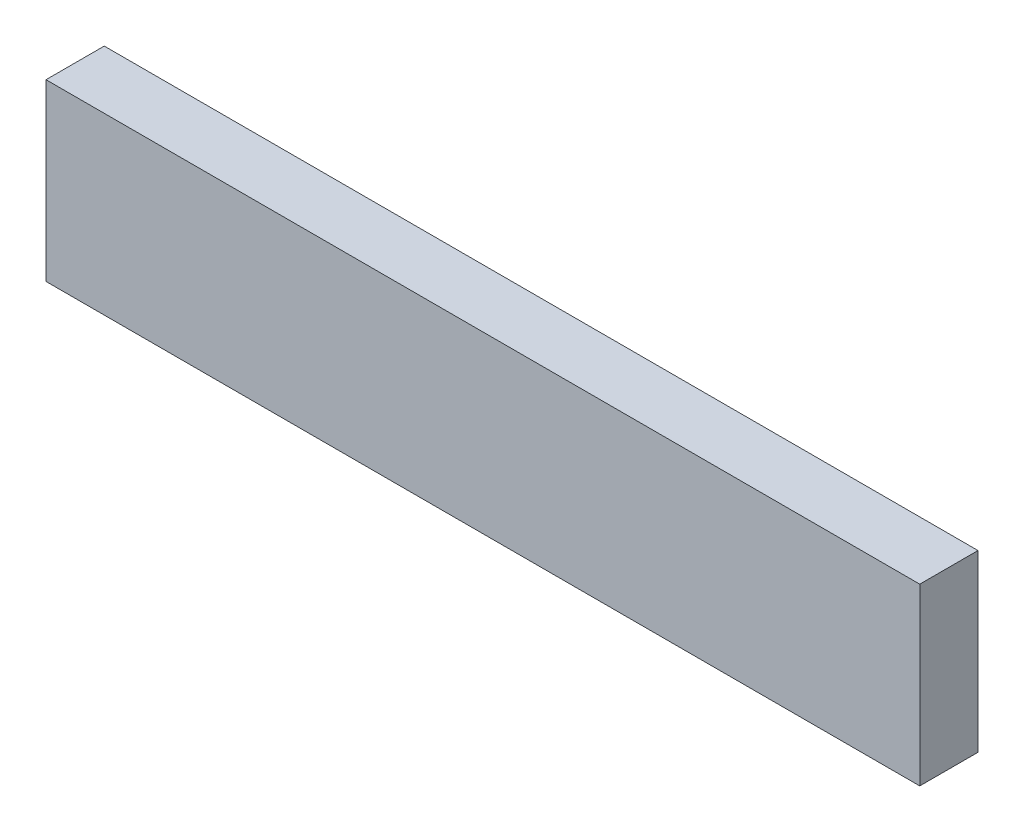
SolidWorks part; units mm, degrees
material "6061-T6 (SS)"
ref_plane "Front Plane" through (0, 0, 0) normal (0, 0, 1) x (1, 0, 0)
ref_plane "Top Plane" through (0, 0, 0) normal (0, 1, 0) x (1, 0, 0)
ref_plane "Right Plane" through (0, 0, 0) normal (1, 0, 0) x (0, 0, -1)
sketch "Sketch1" plane through (0, 0, 0) normal (0, 0, 1) x (1, 0, 0)
  line L1 (-95.25, -19.05) -> (95.25, -19.05)
  line L2 (-95.25, -19.05) -> (-95.25, 19.05)
  line L3 (-95.25, 19.05) -> (95.25, 19.05)
  line L4 (95.25, -19.05) -> (95.25, 19.05)
  line L5 (-95.25, -19.05) -> (95.25, 19.05) construction
  line L6 (-95.25, 19.05) -> (95.25, -19.05) construction
  point P0 (0, 0)
  dimension "D1" = 38.1
  dimension "D2" = 190.5
extrude "Boss-Extrude1" add sketch "Sketch1" along normal blind 12.7 contours L4 L3 L2 L1 region at (0, 0, 0)
